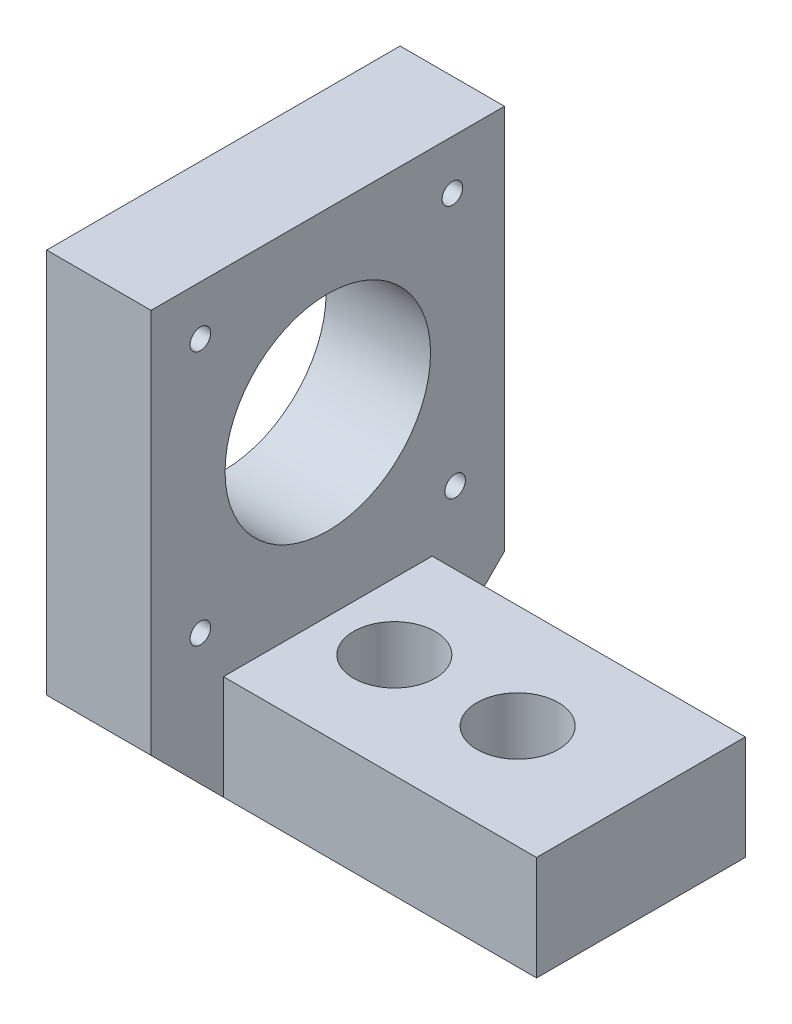
SolidWorks part; units mm, degrees
ref_plane "Front Plane" through (0, 0, 0) normal (0, 0, 1) x (1, 0, 0)
ref_plane "Top Plane" through (0, 0, 0) normal (0, 1, 0) x (1, 0, 0)
ref_plane "Right Plane" through (0, 0, 0) normal (1, 0, 0) x (0, 0, -1)
sketch "Sketch1" plane through (0, 0, 0) normal (0, 1, 0) x (1, 0, 0)
  line L1 (-25.4, -12.7) -> (25.4, -12.7)
  line L2 (-25.4, -12.7) -> (-25.4, 12.7)
  line L3 (-25.4, 12.7) -> (25.4, 12.7)
  line L4 (25.4, -12.7) -> (25.4, 12.7)
  line L5 (-25.4, -12.7) -> (25.4, 12.7) construction
  line L6 (-25.4, 12.7) -> (25.4, -12.7) construction
  point P0 (0, 0)
  dimension "D1" = 25.4
  dimension "D2" = 50.8
extrude "Boss-Extrude1" add sketch "Sketch1" along normal blind 12.7
sketch "Sketch2" plane through (-25.4, 0, 0) normal (-1, 0, 0) x (0, 0, 1)
  line L1 (-15.5, 18.7) -> (15.5, 18.7) construction
  line L2 (-15.5, 18.7) -> (-15.5, 49.7) construction
  line L3 (-15.5, 49.7) -> (15.5, 49.7) construction
  line L4 (15.5, 18.7) -> (15.5, 49.7) construction
  line L5 (-15.5, 18.7) -> (15.5, 49.7) construction
  line L6 (-15.5, 49.7) -> (15.5, 18.7) construction
  line L7 (-12.7, 12.7) -> (12.7, 12.7) construction
  line L8 (-21.5, 12.7) -> (21.5, 12.7)
  line L9 (-21.5, 12.7) -> (-21.5, 55.7)
  line L10 (-21.5, 55.7) -> (21.5, 55.7)
  line L11 (21.5, 12.7) -> (21.5, 55.7)
  line L12 (-21.5, 12.7) -> (21.5, 55.7) construction
  line L13 (-21.5, 55.7) -> (21.5, 12.7) construction
  circle A0 centre (0, 34.2) radius 12.5
  point P0 (0, 34.2)
  point P5 (0, 34.2)
  dimension "D3" = 25
  dimension "D1" = 31
  dimension "D2" = 43
extrude "Boss-Extrude2" add sketch "Sketch2" against normal blind 12.7
chamfer "Chamfer1" distance 12.7 angle 45 2 edges at (-19.05, 12.7, 12.7) (-19.05, 12.7, -12.7)
hole_wizard "Tap Drill for M3x0.5 Tap1" positions "Sketch3" profile "Sketch4" hole size "M3x0.5" standard "ANSI Metric" end condition through all
sketch "Sketch3" plane through (-25.4, 0, 0) normal (-1, 0, 0) x (0, 0, 1)
  line L0 (-15.5, 49.7) -> (15.5, 49.7) construction
  point P0 (-15.1608, 49.7)
  point P4 (15.5, 49.7)
  point P7 (15.5, 18.7)
  point P10 (-15.5, 18.7)
sketch "Sketch4" plane through (-25.4, 49.7, -15.1608) normal (0, 1, 0) x (0, 0, 1)
  line L0 (0, 0) -> (0, 50.8)
  line L1 (0, 50.8) -> (1.25, 50.8)
  line L2 (1.25, 50.8) -> (1.25, 0)
  line L5 (1.25, 0) -> (0, 0)
  line L11 (0, -6.35) -> (0, 107.95) construction
  dimension "Thru Hole Dia." = 2.5
  dimension "Thru Hole Depth" = 50.8
sketch "Sketch5" plane through (0, 12.7, 0) normal (0, 1, 0) x (1, 0, 0)
  line L0 (25.4, 0) -> (-12.7, 0) construction
  line L1 (25.4, -12.7) -> (25.4, 12.7) construction
  line L2 (-12.7, -21.5) -> (-12.7, 21.5) construction
  point P6 (10.4, 0)
  point P7 (-4.6, 0)
  dimension "D1" = 15
  dimension "D2" = 15
hole_wizard "1/4 Clearance Hole1" positions "Sketch6" profile "Sketch7" hole size "1/4" standard "ANSI Inch" end condition through all
sketch "Sketch6" plane through (0, 12.7, 0) normal (0, 1, 0) x (1, 0, 0)
  point P0 (-4.6, 0)
  point P3 (10.4, 0)
sketch "Sketch7" plane through (-4.6, 12.7, 0) normal (1, 0, 0) x (0, 0, 1)
  line L0 (0, 0) -> (0, 12.7)
  line L1 (0, 12.7) -> (3.3782, 12.7)
  line L2 (3.3782, 12.7) -> (3.3782, 0)
  line L5 (3.3782, 0) -> (0, 0)
  line L11 (0, -6.35) -> (0, 107.95) construction
  dimension "Thru Hole Dia." = 6.7564
  dimension "Thru Hole Depth" = 12.7
sketch "Sketch8" plane through (0, 12.7, 0) normal (0, 1, 0) x (1, 0, 0)
  circle A0 centre (-4.6, 0) radius 4.953
  circle A1 centre (10.4, 0) radius 4.953
  dimension "D1" = 9.906
  dimension "D2" = 9.906
extrude "Cut-Extrude1" cut sketch "Sketch8" against normal blind 7.112
